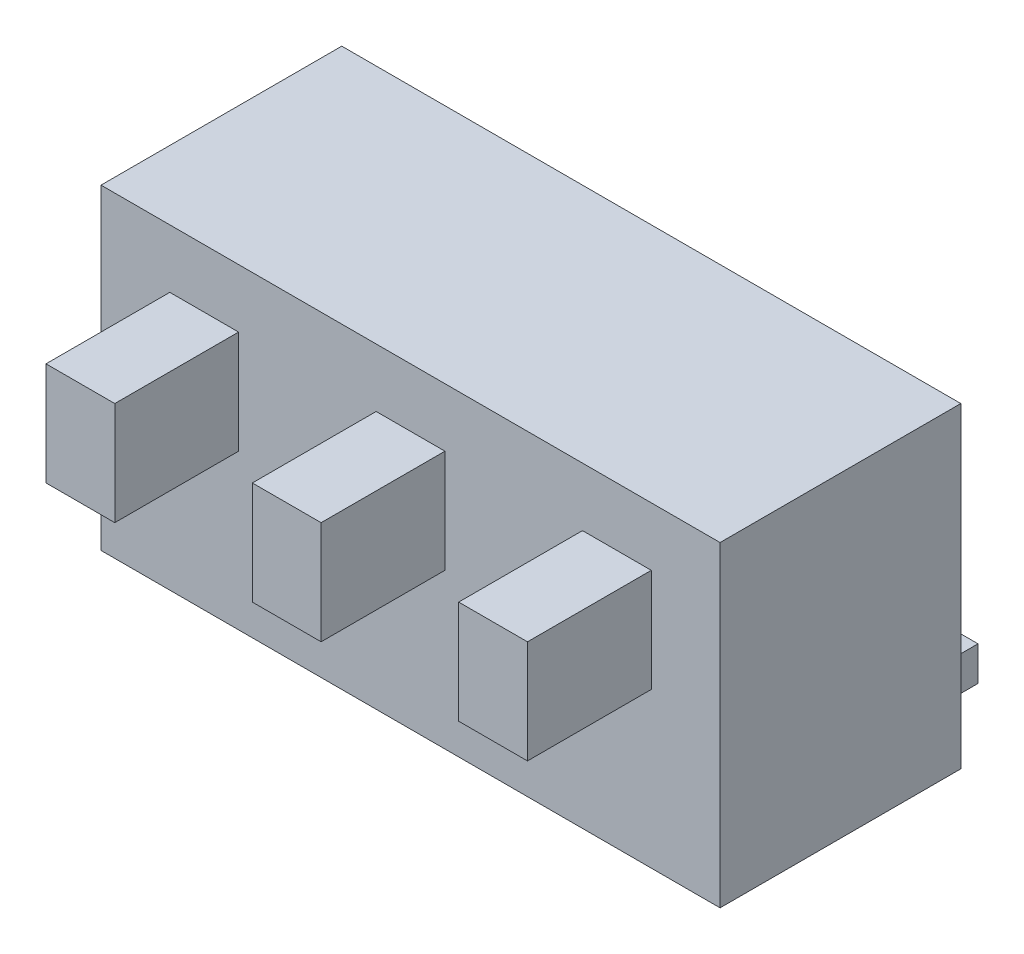
SolidWorks part; units mm, degrees
ref_plane "Front Plane" through (0, 0, 0) normal (0, 0, 1) x (1, 0, 0)
ref_plane "Top Plane" through (0, 0, 0) normal (0, 1, 0) x (1, 0, 0)
ref_plane "Right Plane" through (0, 0, 0) normal (1, 0, 0) x (0, 0, -1)
ref_axis "X-Axis" through (-88.99, 0, 0) along (1, 0, 0)
ref_axis "Y-Axis" through (0, 55, 0) along (0, -1, 0)
ref_axis "Z-Axis" through (0, 0, -88.99) along (0, 0, 1)
sketch "Sketch1" plane through (0, 0, 0) normal (0, 1, 0) x (1, 0, 0)
  line L1 (-4.5, -1.75) -> (4.5, -1.75)
  line L2 (-4.5, -1.75) -> (-4.5, 1.75)
  line L3 (-4.5, 1.75) -> (4.5, 1.75)
  line L4 (4.5, -1.75) -> (4.5, 1.75)
  line L5 (-4.5, -1.75) -> (4.5, 1.75) construction
  line L6 (-4.5, 1.75) -> (4.5, -1.75) construction
  point P0 (0, 0)
  dimension "D1" = 3.5
  dimension "D2" = 9
extrude "Boss-Extrude1" add sketch "Sketch1" along normal blind 4.6
sketch "Sketch2" plane through (0, 0, 1.75) normal (0, 0, 1) x (1, 0, 0)
  line L0 (0, 0) -> (0, 3) construction
  line L2 (-0.5, 2.25) -> (0.5, 2.25)
  line L3 (-0.5, 2.25) -> (-0.5, 3.75)
  line L4 (-0.5, 3.75) -> (0.5, 3.75)
  line L5 (0.5, 2.25) -> (0.5, 3.75)
  line L6 (-0.5, 2.25) -> (0.5, 3.75) construction
  line L7 (-0.5, 3.75) -> (0.5, 2.25) construction
  line L8 (-4.5, 0) -> (4.5, 0) construction
  dimension "D1" = 1
  dimension "D2" = 1.5
  dimension "D3" = 3
extrude "Boss-Extrude2" add sketch "Sketch2" along normal blind 1.8
pattern_linear "LPattern1" count 2 spacing 3 along (1, 0, 0) count 2 spacing 3 along (-1, 0, 0) of "Boss-Extrude2"
sketch "Sketch5" plane through (0, 0, 0) normal (0, -1, 0) x (1, 0, 0)
  line L0 (0, -1.75) -> (0, -1.15) construction
  line L1 (4.5, -1.75) -> (-4.5, -1.75) construction
  line L2 (-1.5, -1.15) -> (1.5, -1.15) construction
  circle A0 centre (-1.5, -1.15) radius 0.35
  circle A1 centre (1.5, -1.15) radius 0.35
  point P8 (0, -1.15)
  dimension "D3" = 0.7
  dimension "D1" = 3
  dimension "D2" = 0.6
extrude "Boss-Extrude4" add sketch "Sketch5" along normal blind 0.7
sketch "Sketch3" plane through (0, 0, -1.75) normal (0, 0, -1) x (-1, 0, 0)
  line L0 (0, 0) -> (0, 0.25) construction
  line L1 (-4.5, 0) -> (4.5, 0) construction
  line L2 (-0.55, 0.5) -> (0.55, 0.5)
  line L3 (-0.55, 0.5) -> (-0.55, 0)
  line L4 (-0.55, 0) -> (0.55, 0)
  line L5 (0.55, 0.5) -> (0.55, 0)
  line L6 (-0.55, 0.5) -> (0.55, 0) construction
  line L7 (-0.55, 0) -> (0.55, 0.5) construction
  dimension "D1" = 0.5
  dimension "D2" = 1.1
extrude "Boss-Extrude3" add sketch "Sketch3" along normal blind 1.2
pattern_linear "LPattern2" count 2 spacing 3 along (1, 0, 0) count 2 spacing 3 along (-1, 0, 0) of "Boss-Extrude3" pattern seed only yes
